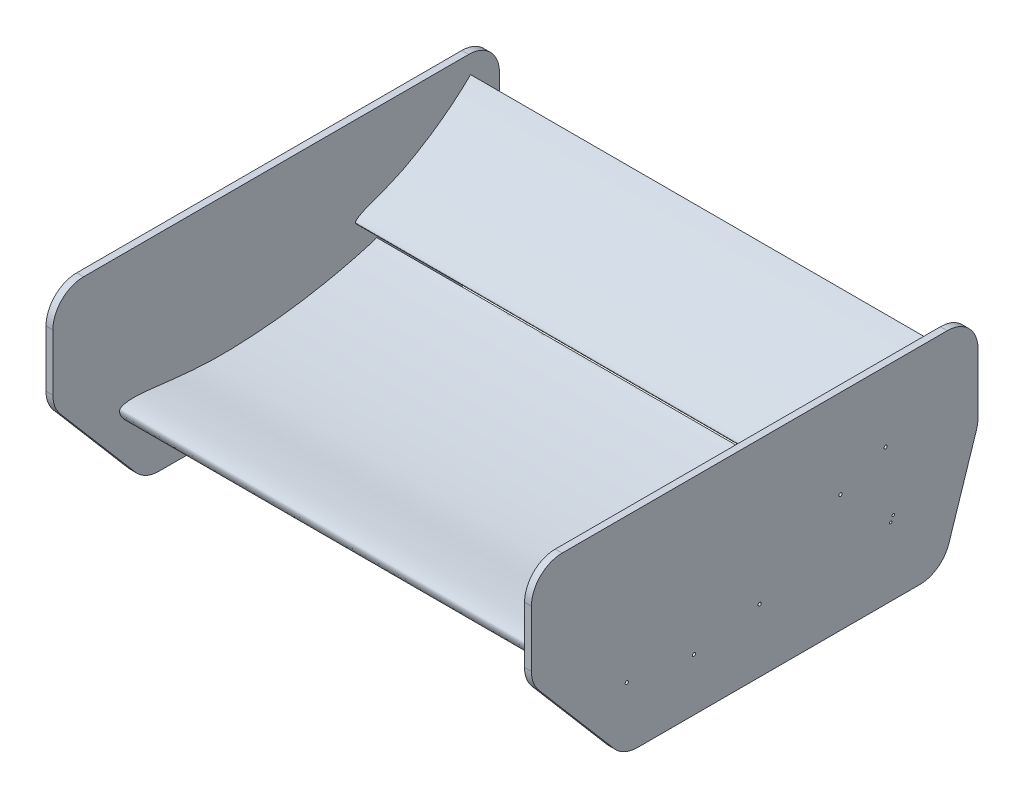
SolidWorks part; units mm, degrees
ref_plane "Front Plane" through (0, 0, 0) normal (0, 0, 1) x (1, 0, 0)
ref_plane "Top Plane" through (0, 0, 0) normal (0, 1, 0) x (1, 0, 0)
ref_plane "Right Plane" through (0, 0, 0) normal (1, 0, 0) x (0, 0, -1)
ref_plane "Soft Top Limit" through (0, 1174.6, 0) normal (0, 1, 0) x (1, 0, 0)
ref_plane "Soft Rear Limit" through (0, 0, -1192.975) normal (0, 0, 1) x (1, 0, 0)
ref_plane "Soft Right Limit" through (-501.65, 0, 0) normal (1, 0, 0) x (0, 0, -1)
ref_plane "Soft Left Limit" through (501.65, 0, 0) normal (1, 0, 0) x (0, 0, -1)
ref_plane "Soft Front Limit" through (0, 0, -165.1) normal (0, 0, 1) x (1, 0, 0)
ref_plane "Slant Limit" through (0, 528.6251, -619.2711) normal (0, -0.6492, 0.7606) x (1, 0, 0)
ref_plane "Bottom" through (0, 476.25, 0) normal (0, 1, 0) x (1, 0, 0)
ref_plane "Midplane" through (0, 0, 0) normal (1, 0, 0) x (0, 0, -1)
curve "Imported Airfoil Curve"
  spline degree 3 poles (0, 2520.0207, 6.126) (0, 2544.889, -1.81) (0, 2521.8965, 7.8839) (0, 2505.3253, 17.7145) (0, 2467.7144, 38.5723) (0, 2424.2142, 62.3813) (0, 2368.0949, 87.8078) (0, 2301.3729, 113.3478) (0, 2223.8362, 140.5377) (0, 2136.6129, 169.2441) (0, 2040.932, 199.097) (0, 1938.2341, 229.6055) (0, 1829.9414, 260.0781) (0, 1717.5266, 289.8586) (0, 1602.4273, 318.1375) (0, 1486.0259, 343.9752) (0, 1369.6902, 366.5754) (0, 1254.3666, 384.7865) (0, 1140.5393, 397.0034) (0, 1028.6357, 403.0127) (0, 919.0585, 402.9406) (0, 812.3986, 397.0375) (0, 709.2785, 385.5985) (0, 610.4299, 369.039) (0, 516.5862, 348.1086) (0, 428.5874, 323.3415) (0, 347.2653, 295.2055) (0, 273.332, 264.2656) (0, 207.4209, 231.0894) (0, 150.0337, 196.3024) (0, 101.596, 160.572) (0, 62.3674, 124.65) (0, 32.4977, 89.3959) (0, 12.0597, 55.6746) (0, 1.683, 26.6201) (0, -0.5567, 6.5526) (0, 0.5894, -3.9947) (0, 1.6947, -9.1451) (0, 2.8711, -12.4915) (0, 3.9449, -14.9776) (0, 4.8993, -16.669) (0, 5.9763, -18.2433) (0, 7.3264, -19.6365) (0, 8.8595, -20.9434) (0, 11.1868, -22.7306) (0, 14.6073, -24.7406) (0, 20.085, -27.4067) (0, 26.8353, -29.9257) (0, 44.6446, -35.1819) (0, 77.8093, -38.8998) (0, 130.2841, -38.2927) (0, 196.3018, -31.4611) (0, 276.2192, -18.4434) (0, 370.8288, 0.8611) (0, 480.7331, 24.811) (0, 605.9792, 50.0099) (0, 745.0759, 74.1542) (0, 895.4497, 95.0846) (0, 1053.6786, 110.004) (0, 1215.6439, 118.3392) (0, 1377.6893, 121.6348) (0, 1537.1174, 120.5125) (0, 1691.5141, 115.2051) (0, 1838.3121, 105.7388) (0, 1975.028, 93.0069) (0, 2099.5942, 78.4581) (0, 2210.5746, 63.1262) (0, 2306.3634, 48.0168) (0, 2387.2069, 33.7158) (0, 2449.0745, 22.0129) (0, 2499.1865, 10.4993) (0, 2520.0207, 6.126) (0, 2544.889, -1.81) (0, 2521.8965, 7.8839) knots -0.016237 -0.007308 -0.001841 0 0.001813 0.006911 0.014576 0.024172 0.035572 0.049013 0.064513 0.081849 0.100772 0.120997 0.142228 0.164173 0.186537 0.209023 0.231367 0.25332 0.274804 0.295858 0.316449 0.336531 0.356033 0.374893 0.39299 0.410197 0.426388 0.441459 0.455334 0.467938 0.479236 0.489204 0.497851 0.505194 0.511308 0.515097 0.516441 0.517273 0.51806 0.518436 0.518797 0.519154 0.519508 0.519887 0.520289 0.52116 0.522116 0.52372 0.525214 0.532575 0.542381 0.554776 0.569931 0.588005 0.609188 0.633329 0.660001 0.688743 0.718873 0.749543 0.780127 0.810209 0.839387 0.867183 0.893104 0.91676 0.937874 0.956199 0.971544 0.983763 0.992692 0.998159 1 1.001813 1.006911 1.014576 periodic
sketch "Airfoils Sketch" plane through (0, 0, 0) normal (1, 0, 0) x (0, 0, -1)
  line L0 (165.1, 1174.6) -> (165.1, 1060.6753) construction
  line L1 (165.1, 1060.6753) -> (663.9798, 476.25) construction
  line L2 (663.9798, 476.25) -> (1192.975, 476.25) construction
  line L3 (1192.975, 476.25) -> (1192.975, 1174.6) construction
  line L4 (1192.975, 1174.6) -> (165.1, 1174.6) construction
  line L5 (509.9361, 1174.6) -> (-509.9361, 1174.6) construction
  line L6 (165.1, 67.0076) -> (165.1, -67.0076) construction
  line L7 (364.7288, 826.8151) -> (873.8134, 230.4351) construction
  line L8 (279.3831, 476.25) -> (-279.3831, 476.25) construction
  line L9 (1192.975, 353.2696) -> (1192.975, -353.2696) construction
  line L10 (414.7055, 818.0274) -> (401.202, 972.3726) construction
  line L11 (945.202, 874.5029) -> (933.446, 1008.8748) construction
  line L12 (939.324, 941.6889) -> (407.9538, 895.2) construction
  line L13 (306.3538, 895.2) -> (1192.975, 895.2) construction
  line L14 (866.0383, 1036.8746) -> (926.5682, 940.0065) construction
  line L15 (1102.685, 1185.4108) -> (1163.8108, 1087.5892) construction
  line L16 (1133.2479, 1136.5) -> (896.3033, 988.4406) construction
  line L21 (176.2614, 1047.6) -> (1192.975, 1047.6) construction
  spline S0 degree 3 poles (935.2529, 940.0507) (940.3147, 942.1548) (935.6767, 939.7163) (932.3848, 937.3638) (924.8872, 932.3286) (916.21, 926.5709) (904.9213, 920.2497) (891.4161, 913.7156) (875.6775, 906.6433) (857.9391, 899.0809) (838.4515, 891.1278) (817.5075, 882.9123) (795.3921, 874.6046) (772.4019, 866.3681) (748.8232, 858.3979) (724.9284, 850.9153) (700.9897, 844.1113) (677.1845, 838.2437) (653.5854, 833.657) (630.2782, 830.4035) (607.3492, 828.4639) (584.9266, 827.7965) (563.1459, 828.3505) (542.1676, 830.0521) (522.1586, 832.7575) (503.3041, 836.37) (485.7865, 840.8065) (469.765, 845.9615) (455.382, 851.7275) (442.7539, 857.9825) (431.9816, 864.5947) (423.1327, 871.4111) (416.2539, 878.2548) (411.376, 884.946) (408.6865, 890.8402) (407.8599, 894.9991) (407.9116, 897.2265) (408.051, 898.3239) (408.2374, 899.0451) (408.4178, 899.5844) (408.5873, 899.9553) (408.7846, 900.3039) (409.0422, 900.6195) (409.3397, 900.9203) (409.7947, 901.3358) (410.4746, 901.8174) (411.5732, 902.4729) (412.9407, 903.1204) (416.5733, 904.5379) (423.4463, 905.9074) (434.4368, 906.7165) (448.3721, 906.4646) (465.3261, 905.1664) (485.4664, 902.8148) (508.8897, 899.7641) (535.5455, 896.7257) (565.0805, 894.155) (596.9177, 892.4579) (630.2914, 892.1587) (664.3294, 893.3038) (698.2942, 895.5048) (731.6326, 898.5836) (763.8436, 902.4482) (794.3904, 907.0475) (822.7695, 912.1503) (848.5739, 917.4165) (871.5218, 922.6042) (891.2949, 927.4743) (907.9553, 931.9087) (920.6916, 935.461) (930.9716, 938.764) (935.2529, 940.0507) (940.3147, 942.1548) (935.6767, 939.7163) knots -0.016237 -0.007308 -0.001841 0 0.001813 0.006911 0.014576 0.024172 0.035572 0.049013 0.064513 0.081849 0.100772 0.120997 0.142228 0.164173 0.186537 0.209023 0.231367 0.25332 0.274804 0.295858 0.316449 0.336531 0.356033 0.374893 0.39299 0.410197 0.426388 0.441459 0.455334 0.467938 0.479236 0.489204 0.497851 0.505194 0.511308 0.515097 0.516441 0.517273 0.51806 0.518436 0.518797 0.519154 0.519508 0.519887 0.520289 0.52116 0.522116 0.52372 0.525214 0.532575 0.542381 0.554776 0.569931 0.588005 0.609188 0.633329 0.660001 0.688743 0.718873 0.749543 0.780127 0.810209 0.839387 0.867183 0.893104 0.91676 0.937874 0.956199 0.971544 0.983763 0.992692 0.998159 1 1.001813 1.006911 1.014576 only from (939.324, 941.6889) to (939.324, 941.6889)
  spline S1 degree 3 poles (1131.7374, 1134.7673) (1133.5995, 1136.953) (1132.0147, 1134.712) (1131.0377, 1132.8312) (1128.7359, 1128.6983) (1126.0553, 1123.9476) (1122.2899, 1118.3128) (1117.5406, 1112.0516) (1111.8769, 1105.0082) (1105.3965, 1097.2604) (1098.1926, 1088.9143) (1090.3713, 1080.0994) (1082.0253, 1070.9629) (1073.254, 1061.6516) (1064.1447, 1052.3247) (1054.7721, 1043.1501) (1045.2175, 1034.2818) (1035.5025, 1025.8823) (1025.5791, 1018.1297) (1015.4749, 1011.0686) (1005.2348, 1004.7108) (994.9285, 999.0671) (984.6313, 994.1461) (974.4357, 989.9515) (964.4538, 986.456) (954.795, 983.6583) (945.5642, 981.5631) (936.8608, 980.159) (928.7768, 979.4298) (921.3956, 979.3461) (914.7955, 979.8704) (909.0446, 980.9475) (904.2067, 982.5058) (900.3389, 984.4687) (897.682, 986.58) (896.3072, 988.3245) (895.8017, 989.3763) (895.6058, 989.9216) (895.5213, 990.3026) (895.4772, 990.5972) (895.4681, 990.8106) (895.4773, 991.0202) (895.5225, 991.2288) (895.5898, 991.4399) (895.7034, 991.742) (895.9061, 992.1285) (896.263, 992.6957) (896.7472, 993.3231) (898.1055, 994.8485) (900.9876, 997.1221) (905.9247, 1000.1133) (912.4884, 1003.3096) (920.7099, 1006.7355) (930.6689, 1010.4274) (942.3265, 1014.5737) (955.4898, 1019.4945) (969.8856, 1025.3183) (985.1482, 1032.0973) (1000.7954, 1039.894) (1016.4092, 1048.5229) (1031.7378, 1057.6271) (1046.5653, 1066.992) (1060.6797, 1076.4556) (1073.8427, 1085.8664) (1085.8742, 1094.9966) (1096.6653, 1103.5909) (1106.1418, 1111.4691) (1114.2121, 1118.4443) (1120.9333, 1124.4758) (1126.0328, 1129.1625) (1130.0452, 1133.1487) (1131.7374, 1134.7673) (1133.5995, 1136.953) (1132.0147, 1134.712) knots -0.016237 -0.007308 -0.001841 0 0.001813 0.006911 0.014576 0.024172 0.035572 0.049013 0.064513 0.081849 0.100772 0.120997 0.142228 0.164173 0.186537 0.209023 0.231367 0.25332 0.274804 0.295858 0.316449 0.336531 0.356033 0.374893 0.39299 0.410197 0.426388 0.441459 0.455334 0.467938 0.479236 0.489204 0.497851 0.505194 0.511308 0.515097 0.516441 0.517273 0.51806 0.518436 0.518797 0.519154 0.519508 0.519887 0.520289 0.52116 0.522116 0.52372 0.525214 0.532575 0.542381 0.554776 0.569931 0.588005 0.609188 0.633329 0.660001 0.688743 0.718873 0.749543 0.780127 0.810209 0.839387 0.867183 0.893104 0.91676 0.937874 0.956199 0.971544 0.983763 0.992692 0.998159 1 1.001813 1.006911 1.014576 only from (1133.2479, 1136.5) to (1133.2479, 1136.5)
  dimension "D1" = 533.4
  dimension "D2" = 279.4
  dimension "D3" = 5
  dimension "D4" = 101.6
  dimension "D5" = 279.4
  dimension "D6" = 38.1
  dimension "D7" = 32
  dimension "D8" = 59.7271
  dimension "D9" = 127
extrude "Extruded Airfoils" add sketch "Airfoils Sketch" along normal offset from surface (487.45 mm away) 14.2 up to plane "Soft Left Limit"
sketch "Endplate Sketch" plane through (501.65, 0, 0) normal (1, 0, 0) x (0, 0, -1)
  line L6 (333.4477, 1174.6) -> (1129.475, 1174.6)
  line L7 (1192.975, 1174.6) -> (165.1, 1174.6) construction
  line L8 (1192.975, 1111.1) -> (1192.975, 986.6717)
  line L9 (1192.975, 476.25) -> (1192.975, 1174.6) construction
  line L11 (1189.8464, 966.9854) -> (1132.8969, 792.34)
  line L12 (1072.5255, 748.5263) -> (489.1772, 748.5263)
  line L19 (440.8805, 770.7991) -> (285.151, 953.2323)
  line L26 (269.9477, 994.4595) -> (269.9477, 1111.1)
  line L28 (165.1, 1060.6753) -> (663.9798, 476.25) construction
  arc A12 (1129.475, 1174.6) -> (1192.975, 1111.1) centre (1129.475, 1111.1) cw
  arc A13 (1192.975, 986.6717) -> (1189.8464, 966.9854) centre (1129.475, 986.6717) cw
  arc A14 (1132.8969, 792.34) -> (1072.5255, 748.5263) centre (1072.5255, 812.0263) cw
  arc A15 (489.1772, 748.5263) -> (440.8805, 770.7991) centre (489.1772, 812.0263) cw
  arc A16 (285.151, 953.2323) -> (269.9477, 994.4595) centre (333.4477, 994.4595) cw
  arc A17 (333.4477, 1174.6) -> (269.9477, 1111.1) centre (333.4477, 1111.1) ccw
  point P16 (1192.975, 1174.6)
  point P19 (1192.975, 976.5799)
  point P29 (269.9477, 1174.6)
  dimension "D1" = 63.5
extrude "Extruded Endplate" add sketch "Endplate Sketch" against normal up to surface (14.2 mm away)
mirror "Mirror" about plane through (0, 0, 0) normal (1, 0, 0) of bodies 106
sketch "Sketch1" plane through (501.65, 0, 0) normal (1, 0, 0) x (0, 0, -1)
  circle A0 centre (466.9636, 876.0274) radius 3.302
extrude "Cut-Extrude1" cut sketch "Sketch1" against normal up to surface (14.2 mm away) up to face at (487.45, 961.8886, -750.0842)
sketch "Sketch2" plane through (501.65, 0, 0) normal (1, 0, 0) x (0, 0, -1)
  circle A0 centre (605.9718, 856.7319) radius 3.302
extrude "Cut-Extrude2" cut sketch "Sketch2" against normal up to surface (14.2 mm away) up to face at (487.45, 961.8886, -750.0842)
sketch "Sketch3" plane through (501.65, 0, 0) normal (1, 0, 0) x (0, 0, -1)
  circle A0 centre (741.5917, 878.9853) radius 3.302
  circle A1 centre (908.6976, 991.5292) radius 3.302
  circle A2 centre (1002.03, 1029.97) radius 3.302
extrude "Cut-Extrude3" cut sketch "Sketch3" against normal up to surface (14.2 mm away) up to face at (487.45, 961.8886, -750.0842)
sketch "Sketch4" plane through (501.65, 0, 0) normal (1, 0, 0) x (0, 0, -1)
  circle A0 centre (1018.0658, 900.3059) radius 2.54
  circle A1 centre (1012.4254, 889.9969) radius 2.54
extrude "Cut-Extrude4" cut sketch "Sketch4" against normal up to surface (14.2 mm away) up to face at (487.45, 961.8886, -750.0842)
sketch "Sketch5" plane through (-485.164, 0, 0) normal (1, 0, 0) x (0, 0, -1)
  circle A0 centre (763.2383, 814.1335) radius 3.2766 construction
  circle A1 centre (763.2383, 849.0585) radius 3.2766 construction
  circle A2 centre (763.2383, 814.1335) radius 3.2766
  circle A3 centre (763.2383, 849.0585) radius 3.2766
extrude "Cut-Extrude5" cut sketch "Sketch5" against normal through all
